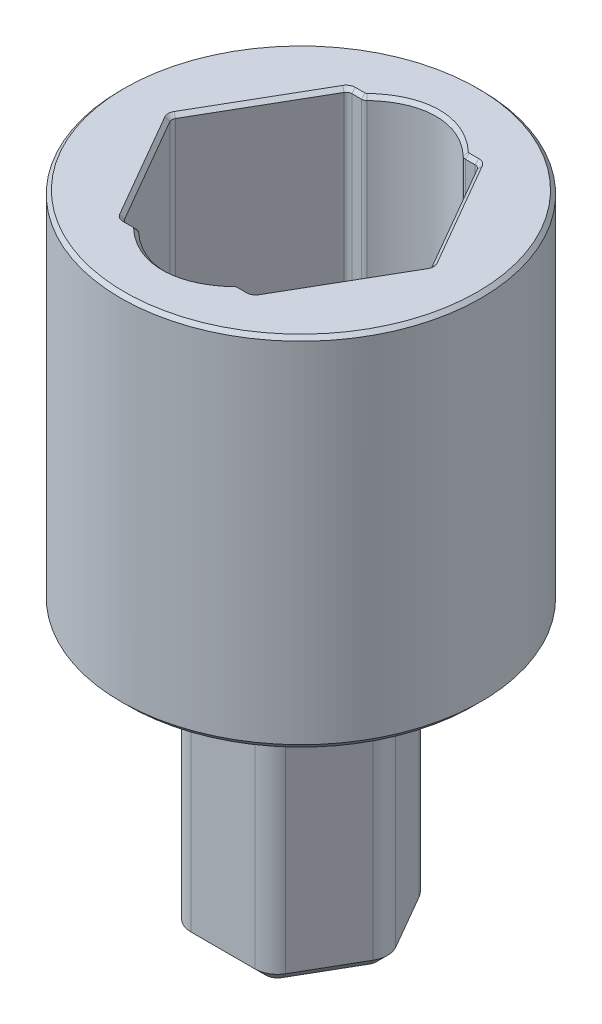
SolidWorks part; units mm, degrees
ref_plane "Front" through (0, 0, 0) normal (0, 0, 1) x (1, 0, 0)
ref_plane "Top" through (0, 0, 0) normal (0, 1, 0) x (1, 0, 0)
ref_plane "Right" through (0, 0, 0) normal (1, 0, 0) x (0, 0, -1)
sketch "Sketch1" plane through (0, 0, 0) normal (0, 0, 1) x (1, 0, 0)
  line L0 (0, 31.8319) -> (0, -31.8319) construction
  line L1 (0, 0) -> (6.35, 0)
  line L2 (6.35, 0) -> (6.35, 19.05)
  line L3 (6.35, 19.05) -> (12.7, 19.05)
  line L4 (12.7, 19.05) -> (12.7, 44.45)
  line L5 (12.7, 44.45) -> (7.9375, 44.45)
  line L6 (7.9375, 44.45) -> (7.9375, 25.4)
  line L7 (7.9375, 25.4) -> (0, 25.4)
  line L8 (0, 25.4) -> (0, 0)
  point P9 (9.525, 19.05)
  dimension "D1" = 19.05
  dimension "D2" = 12.7
  dimension "D3" = 6.35
  dimension "D4" = 19.05
  dimension "D5" = 15.875
  dimension "D6" = 25.4
revolve "Revolve1" add sketch "Sketch1" angle 360 about L0
sketch "Sketch2" plane through (0, 0, 0) normal (0, -1, 0) x (1, 0, 0)
  line L1 (3.175, 5.4993) -> (-3.175, 5.4993)
  line L2 (-3.175, 5.4993) -> (-6.35, 0)
  line L3 (-6.35, 0) -> (-3.175, -5.4993)
  line L4 (-3.175, -5.4993) -> (3.175, -5.4993)
  line L5 (3.175, -5.4993) -> (6.35, 0)
  line L6 (6.35, 0) -> (3.175, 5.4993)
  circle A0 centre (0, 0) radius 6.35
  circle A1 centre (0, 0) radius 6.35 construction
  circle M7 centre (0, 0) radius 6.35
extrude "Cut-Extrude1" cut sketch "Sketch2" against normal up to surface (19.05 mm away) contours L2 M7 | L1 M7 | L6 M7 | L5 M7 | L4 M7 | L3 M7 region at (5.059, 0, 2.9208) region at (0, 0, 5.8416) region at (-5.059, 0, 2.9208) region at (5.059, 0, -2.9208) region at (-5.059, 0, -2.9208) region at (0, 0, -5.8416) up to face at (-12.7, 19.05, 0)
sketch "Sketch3" plane through (0, 44.45, 0) normal (0, 1, 0) x (1, 0, 0)
  line L1 (4.5827, 7.9375) -> (-4.5827, 7.9375)
  line L2 (-4.5827, 7.9375) -> (-9.1654, 0)
  line L3 (-9.1654, 0) -> (-4.5827, -7.9375)
  line L4 (-4.5827, -7.9375) -> (4.5827, -7.9375)
  line L5 (4.5827, -7.9375) -> (9.1654, 0)
  line L6 (9.1654, 0) -> (4.5827, 7.9375)
  circle A0 centre (0, 0) radius 7.9375 construction
  circle A1 centre (0, 0) radius 7.9375 construction
extrude "Cut-Extrude2" cut sketch "Sketch3" against normal up to surface (19.05 mm away) up to face at (-7.9375, 25.4, 0)
sketch "Sketch4" plane through (0, 44.45, 0) normal (0, 1, 0) x (1, 0, 0)
  ellipse E0 centre (0, 0) end of major axis (0, 9.525) minor radius 6.35
  point P1 (0, 0)
  dimension "D1" = 19.05
  dimension "D2" = 12.7
extrude "Cut-Extrude3" cut sketch "Sketch4" against normal up to surface (19.05 mm away) up to face at (0, 25.4, 0)
fillet "Fillet1" radius 0.3969 20 edges at (4.0464, 25.4, 7.9375) (4.0464, 25.4, -7.9375) (-4.0464, 25.4, -7.9375) (0, 25.4, 9.525) (-6.8741, 25.4, -3.9688) (0, 25.4, -9.525) (6.8741, 25.4, -3.9688) (6.8741, 25.4, 3.9688) (-4.0464, 25.4, 7.9375) (-6.8741, 25.4, 3.9688) (3.5101, 34.925, 7.9375) (-3.5101, 34.925, 7.9375) (3.5101, 34.925, -7.9375) (-3.5101, 34.925, -7.9375) (-9.1654, 34.925, 0) (-4.5827, 34.925, 7.9375) (4.5827, 34.925, 7.9375) (9.1654, 34.925, 0) (4.5827, 34.925, -7.9375) (-4.5827, 34.925, -7.9375)
fillet "Fillet2" radius 1.5875 12 edges at (4.7625, 19.05, -2.7496) (4.7625, 19.05, 2.7496) (0, 19.05, -5.4993) (0, 19.05, 5.4993) (-4.7625, 19.05, -2.7496) (-4.7625, 19.05, 2.7496) (3.175, 9.525, -5.4993) (6.35, 9.525, 0) (3.175, 9.525, 5.4993) (-6.35, 9.525, 0) (-3.175, 9.525, -5.4993) (-3.175, 9.525, 5.4993)
chamfer "Chamfer1" distance 0.762 angle 45 12 edges at (-3.0522, 0, -5.2866) (-4.7625, 0, -2.7496) (-6.1044, 0, 0) (-4.7625, 0, 2.7496) (-3.0522, 0, 5.2866) (0, 0, 5.4993) (3.0522, 0, 5.2866) (4.7625, 0, 2.7496) (6.1044, 0, 0) (4.7625, 0, -2.7496) (3.0522, 0, -5.2866) (0, 0, -5.4993)
fillet "Chamfer2" radius 0.508 1 edges at (-12.7, 19.05, 0) profile chamfer
chamfer "Chamfer3" distance 0.254 angle 45 21 edges at (6.8741, 44.45, 3.9688) (9.104, 44.45, 0) (4.552, 44.45, 7.8843) (6.8741, 44.45, -3.9688) (4.0124, 44.45, 7.9375) (4.552, 44.45, -7.8843) (3.524, 44.45, 7.9658) (4.0124, 44.45, -7.9375) (0, 44.45, 9.525) (3.524, 44.45, -7.9658) (-3.524, 44.45, 7.9658) (0, 44.45, -9.525) (-4.0124, 44.45, 7.9375) (-3.524, 44.45, -7.9658) (-4.552, 44.45, 7.8843) (-4.0124, 44.45, -7.9375) (-6.8741, 44.45, 3.9688) (-4.552, 44.45, -7.8843) (-9.104, 44.45, 0) (-6.8741, 44.45, -3.9688) (-12.7, 44.45, 0)
